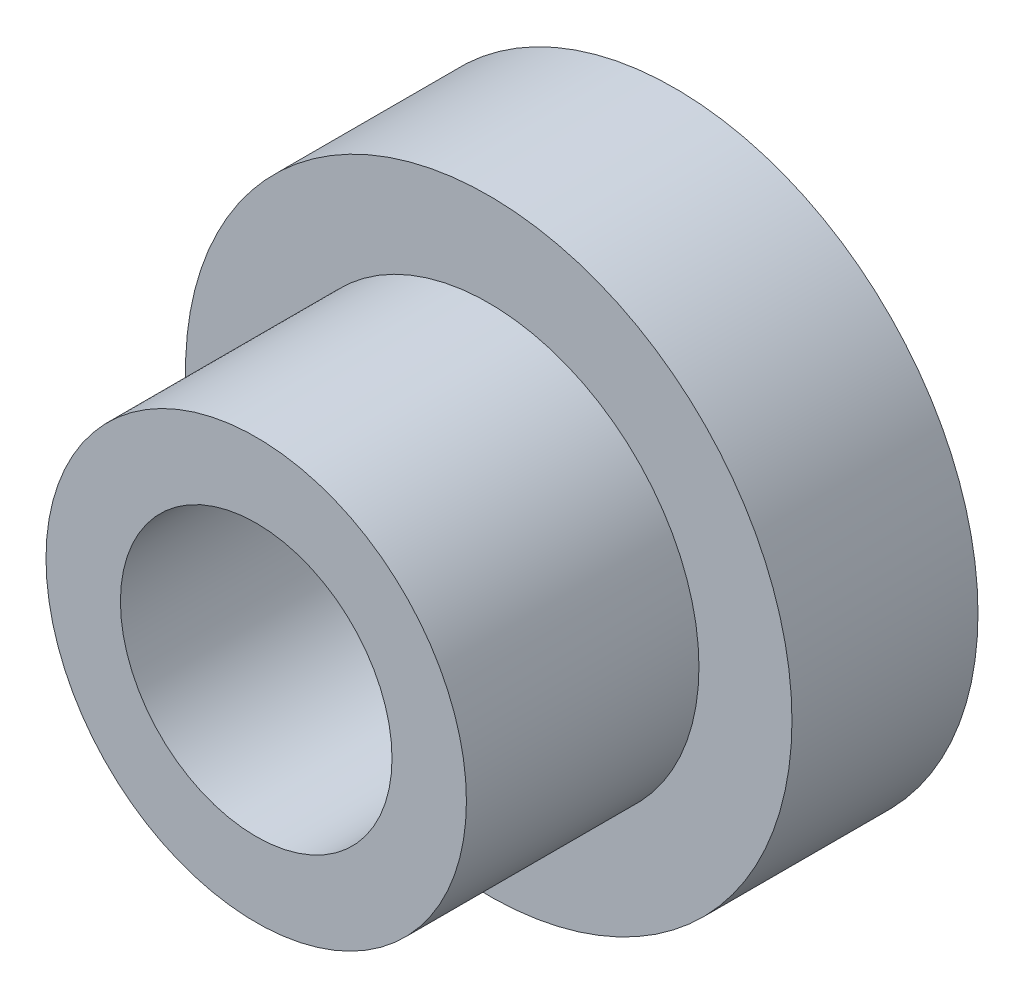
SolidWorks part; units mm, degrees
ref_plane "Front Plane" through (0, 0, 0) normal (0, 0, 1) x (1, 0, 0)
ref_plane "Top Plane" through (0, 0, 0) normal (0, 1, 0) x (1, 0, 0)
ref_plane "Right Plane" through (0, 0, 0) normal (1, 0, 0) x (0, 0, -1)
sketch "Sketch1" plane through (0, 0, 0) normal (0, 0, 1) x (1, 0, 0)
  circle A0 centre (0, 0) radius 16.3
  circle A1 centre (0, 0) radius 11.3
  circle A2 centre (0, 0) radius 7.3
  dimension "D1" = 22.6
  dimension "D2" = 5
  dimension "D3" = 4
extrude "Boss-Extrude1" add sketch "Sketch1" along normal blind 17.5 contours A1 A2 region at (-10.9804, 0, 0)
extrude "Boss-Extrude2" add sketch "Sketch1<4>" against normal blind 10 from offset 5 contours A0 A1 region at (-15.839, 0, 0)
sketch "Sketch1<4>" plane through (0, 0, 0) normal (0, 0, 1) x (1, 0, 0) same geometry as "Sketch1"
